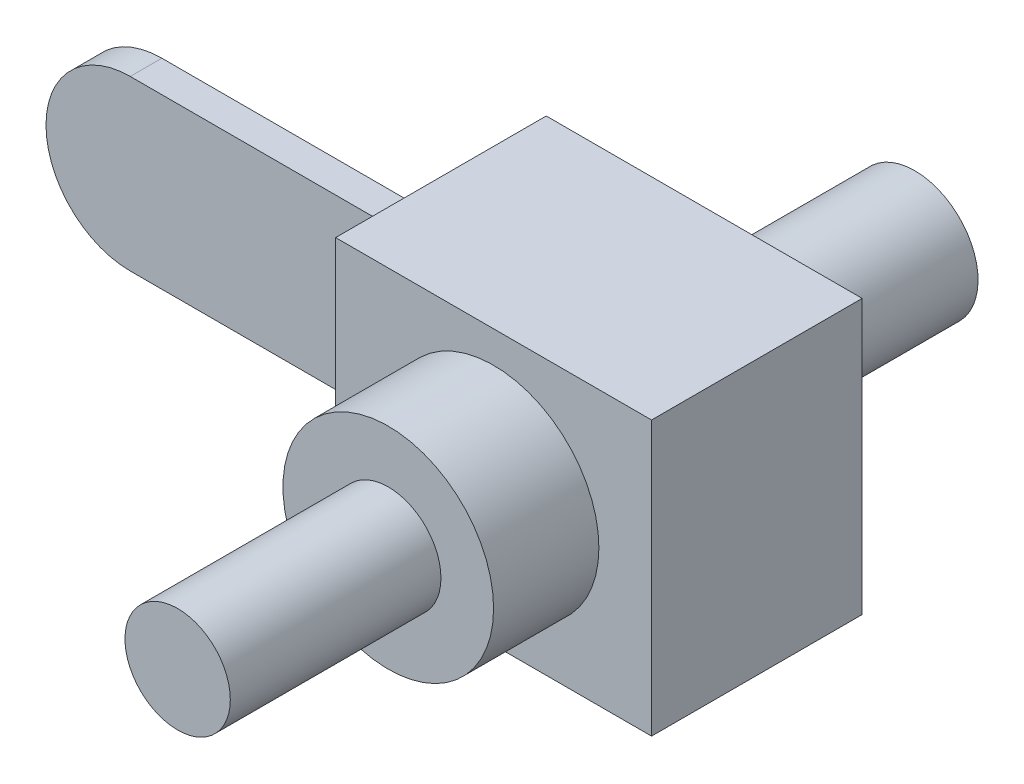
SolidWorks part; units mm, degrees
ref_plane "Front Plane" through (0, 0, 0) normal (0, 0, 1) x (1, 0, 0)
ref_plane "Top Plane" through (0, 0, 0) normal (0, 1, 0) x (1, 0, 0)
ref_plane "Right Plane" through (0, 0, 0) normal (1, 0, 0) x (0, 0, -1)
sketch "Sketch1" plane through (0, 0, 0) normal (0, 0, 1) x (1, 0, 0)
  line L0 (0, 40) -> (140, 40)
  line L1 (140, 40) -> (140, -40)
  line L2 (140, -40) -> (0, -40)
  arc A0 (0, 40) -> (0, -40) centre (0, 0) ccw
  dimension "D1" = 80
  dimension "180" = 140
extrude "Boss-Extrude1" add sketch "Sketch1" along normal mid plane 15
sketch "Sketch3" plane through (140, 0, 0) normal (1, 0, 0) x (0, 0, -1)
  line L1 (-50, 65) -> (50, 65)
  line L2 (-50, 65) -> (-50, -65)
  line L3 (-50, -65) -> (50, -65)
  line L4 (50, 65) -> (50, -65)
  line L5 (-50, 65) -> (50, -65) construction
  line L6 (-50, -65) -> (50, 65) construction
  point P0 (0, 0)
  dimension "D1" = 100
  dimension "D2" = 130
extrude "Boss-Extrude2" add sketch "Sketch3" along normal blind 150
sketch "Sketch4" plane through (0, 0, -50) normal (0, 0, -1) x (-1, 0, 0)
  line L0 (-290, 65) -> (-140, 65) construction
  circle A0 centre (-215, 0) radius 30
  point P5 (-215, 65)
  dimension "D1" = 60
extrude "Boss-Extrude3" add sketch "Sketch4" along normal blind 100
sketch "Sketch5" plane through (0, 0, 50) normal (0, 0, 1) x (1, 0, 0)
  line L0 (290, -65) -> (140, -65) construction
  circle A0 centre (215, 0) radius 50
  point P5 (215, -65)
  dimension "D1" = 100
extrude "Boss-Extrude4" add sketch "Sketch5" along normal blind 50
sketch "Sketch6" plane through (0, 0, 100) normal (0, 0, 1) x (1, 0, 0)
  circle A0 centre (215, 0) radius 25
extrude "Boss-Extrude5" add sketch "Sketch6" along normal blind 100
sketch "Sketch8" plane through (0, 0, -7.5) normal (0, 0, -1) x (-1, 0, 0)
  point P0 (0, 0)
